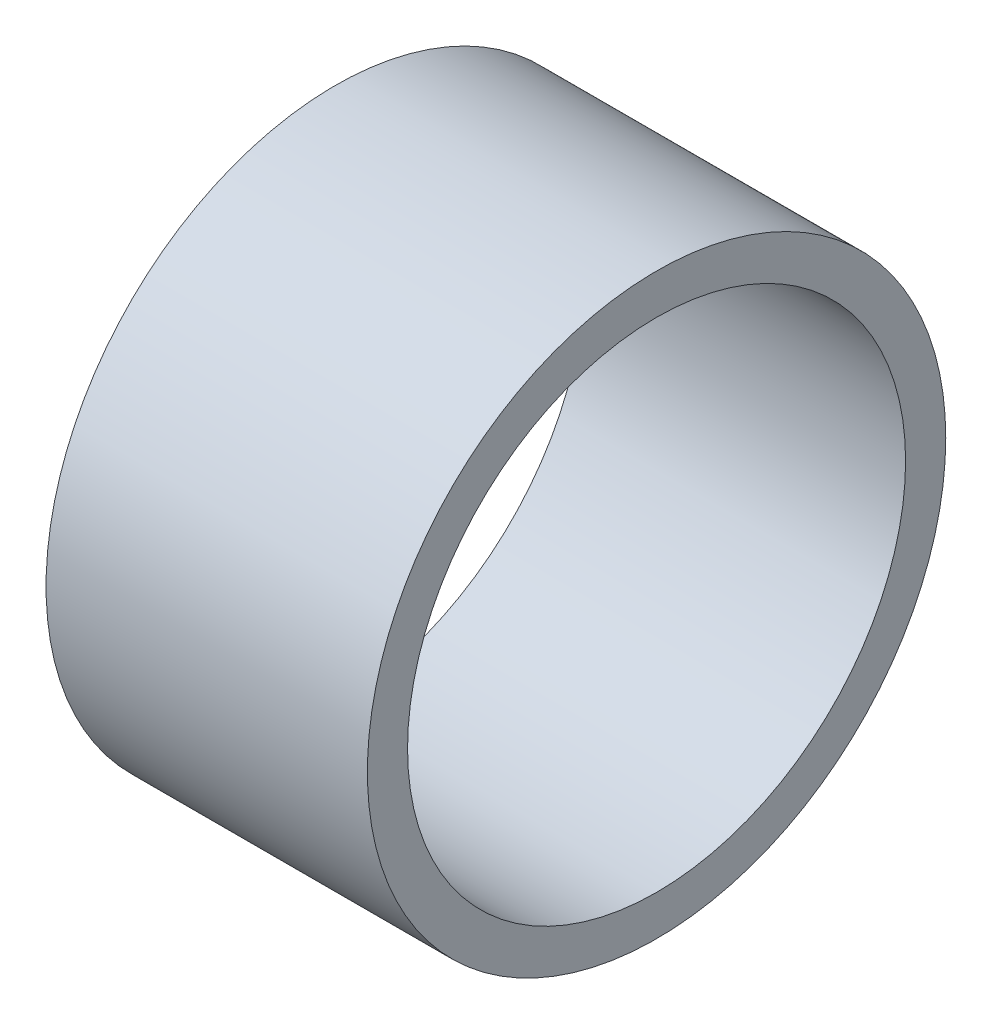
SolidWorks part; units mm, degrees
material "AISI 1020"
ref_plane "Front Plane" through (0, 0, 0) normal (0, 0, 1) x (1, 0, 0)
ref_plane "Top Plane" through (0, 0, 0) normal (0, 1, 0) x (1, 0, 0)
ref_plane "Right Plane" through (0, 0, 0) normal (1, 0, 0) x (0, 0, -1)
sketch "Sketch1" plane through (0, 0, 0) normal (1, 0, 0) x (0, 0, -1)
  circle A0 centre (0, 0) radius 22.86
  circle A1 centre (0, 0) radius 19.685
  dimension "D1" = 45.72
  dimension "D2" = 3.175
extrude "Boss-Extrude1" add sketch "Sketch1" along normal mid plane 25.4
ref_plane "Plane1" through (0, -22.86, 0) normal (0, -1, 0) x (-1, 0, 0)
ref_plane "Plane2" through (0, 0, -22.86) normal (0, 0, -1) x (-1, 0, 0)
